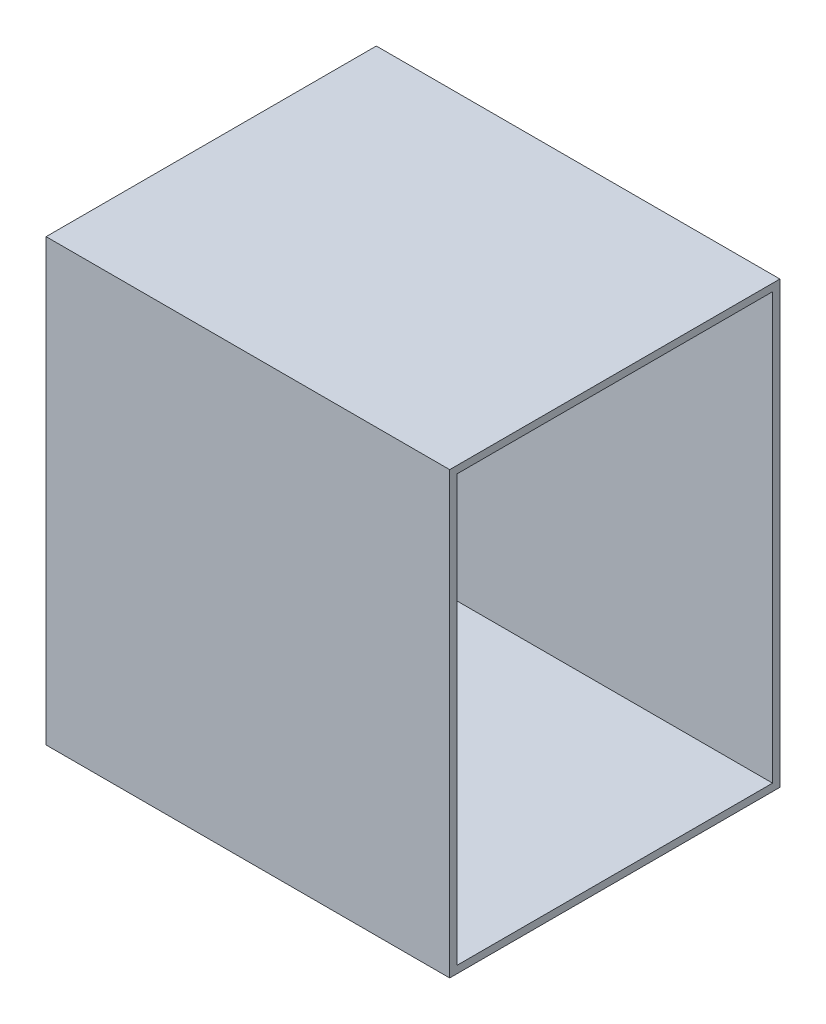
SolidWorks part; units mm, degrees
ref_plane "Front Plane" through (0, 0, 0) normal (0, 0, 1) x (1, 0, 0)
ref_plane "Top Plane" through (0, 0, 0) normal (0, 1, 0) x (1, 0, 0)
ref_plane "Right Plane" through (0, 0, 0) normal (1, 0, 0) x (0, 0, -1)
sketch "Sketch1" plane through (-0.1583, 0, 0) normal (1, 0, 0) x (0, 0, -1)
  line L0 (-0.6034, 109.0184) -> (-0.6034, -10.9816) construction
  line L1 (-90.6034, 109.0184) -> (-0.6034, 109.0184) construction
  line L2 (-90.6034, 109.0184) -> (-90.6034, -10.9816) construction
  line L3 (-90.6034, -10.9816) -> (-0.6034, -10.9816) construction
  line L4 (-0.6034, 109.0184) -> (-0.6034, -10.9816)
  line L5 (-90.6034, 109.0184) -> (-0.6034, 109.0184)
  line L6 (-90.6034, 109.0184) -> (-90.6034, -10.9816)
  line L7 (-90.6034, -10.9816) -> (-0.6034, -10.9816)
  line L8 (-88.6034, -8.9816) -> (-2.6034, -8.9816)
  line L9 (-2.6034, 107.0184) -> (-2.6034, -8.9816)
  line L10 (-88.6034, 107.0184) -> (-2.6034, 107.0184)
  line L11 (-88.6034, 107.0184) -> (-88.6034, -8.9816)
  dimension "D1" = 2
extrude "Boss-Extrude1" add sketch "Sketch1" along normal blind 110
